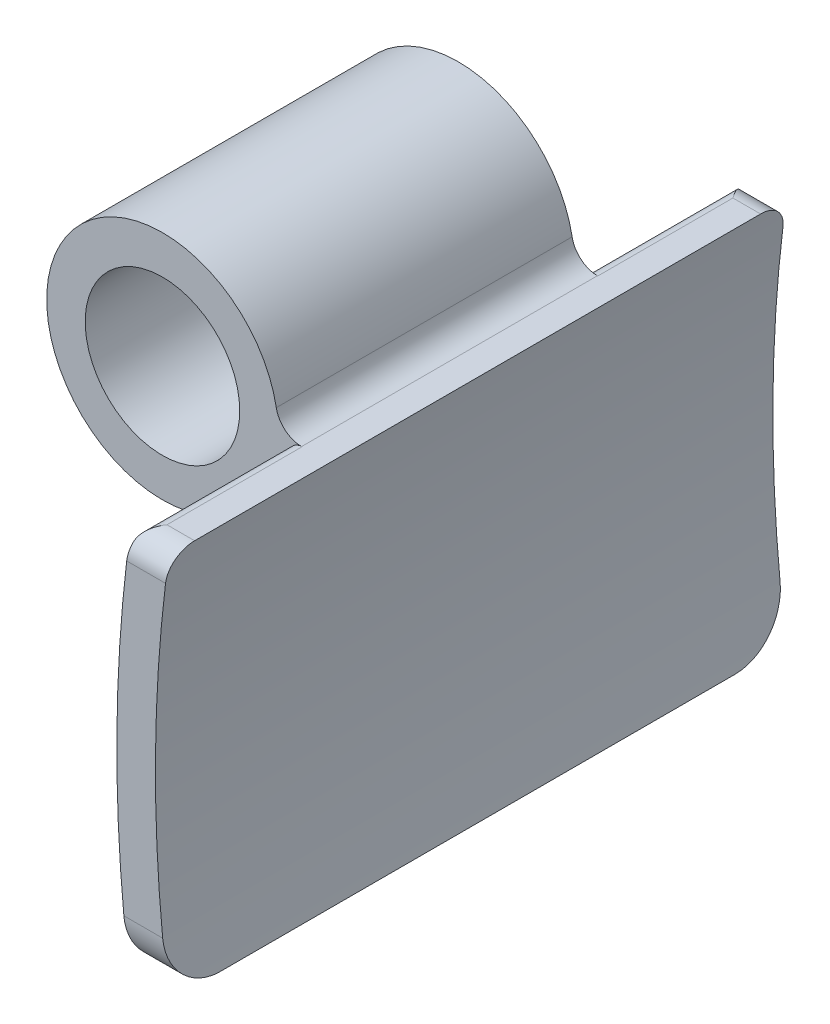
SolidWorks part; units mm, degrees
material "No.2 BRASS"
ref_plane "Front Plane" through (0, 0, 0) normal (0, 0, 1) x (1, 0, 0)
ref_plane "Top Plane" through (0, 0, 0) normal (0, 1, 0) x (1, 0, 0)
ref_plane "Right Plane" through (0, 0, 0) normal (1, 0, 0) x (0, 0, -1)
sketch "Sketch1" plane through (0, 0, 0) normal (0, 0, 1) x (1, 0, 0)
  line L0 (1.4037, 19.6911) -> (4.8697, 19.6911)
  line L1 (4.8697, -27.9339) -> (0.0619, -27.9339)
  arc A0 (4.8697, 19.6911) -> (4.8697, -27.9339) centre (174.658, -4.1214) ccw
  arc A1 (-1.7184, 22.2889) -> (-8.5674, 7.3507) centre (-15.7678, 19.6911) ccw
  arc A2 (-1.4087, 3.0435) -> (0.0619, -27.9339) centre (174.658, -4.1214) ccw
  arc A3 (-8.5674, 7.3507) -> (-1.4087, 3.0435) centre (-6.1673, 3.2372) cw
  arc A4 (1.4037, 19.6911) -> (-1.7184, 22.2889) centre (1.4037, 22.8661) cw
  arc A5 (0.1534, 20.3526) -> (0.1534, -28.5953) centre (174.658, -4.1214) ccw construction
  point P14 (-1.4803, 19.6911)
  dimension "D1" = 171.45
  dimension "D2" = 28.575
  dimension "D5" = 4.7625
  dimension "D6" = 3.175
  dimension "D3" = 20.6375
  dimension "D7" = 47.625
  dimension "D8" = 23.8125
  dimension "D4" = 4.7625
extrude "Boss-Extrude1" add sketch "Sketch1" along normal mid plane 36.5125
sketch "Sketch2" plane through (0, 0, 18.2562) normal (0, 0, 1) x (1, 0, 0)
  arc A0 (-1.7184, 22.2889) -> (-8.5674, 7.3507) centre (-15.7678, 19.6911) ccw construction
  arc A1 (-1.7184, 22.2889) -> (-8.5674, 7.3507) centre (-15.7678, 19.6911) ccw
  circle A2 centre (-15.7678, 19.6911) radius 9.5377
  dimension "D1" = 19.0754
extrude "Cut-Extrude1" cut sketch "Sketch2" against normal through all contours A2
sketch "Sketch4" plane through (0, 0, 18.2562) normal (0, 0, 1) x (1, 0, 0)
  line L0 (0.0619, -27.9339) -> (4.8697, -27.9339) construction
  line L1 (4.8697, 19.6911) -> (1.4037, 19.6911) construction
  line L2 (0.0619, -27.9339) -> (4.8697, -27.9339)
  line L3 (4.8697, 19.6911) -> (1.4037, 19.6911)
  line L4 (4.8697, 19.6911) -> (0.1534, 20.3526)
  line L5 (4.8697, -27.9339) -> (0.1534, -28.5953)
  arc A1 (-1.4087, 3.0435) -> (-8.5674, 7.3507) centre (-6.1673, 3.2372) ccw construction
  arc A2 (-1.4087, 3.0435) -> (0.0619, -27.9339) centre (174.658, -4.1214) ccw construction
  arc A3 (4.8697, 19.6911) -> (4.8697, -27.9339) centre (174.658, -4.1214) ccw construction
  arc A4 (-1.7184, 22.2889) -> (1.4037, 19.6911) centre (1.4037, 22.8661) ccw construction
  arc A5 (-1.7184, 22.2889) -> (-8.5674, 7.3507) centre (-15.7678, 19.6911) ccw construction
  arc A6 (-1.4087, 3.0435) -> (-8.5674, 7.3507) centre (-6.1673, 3.2372) ccw
  arc A7 (-1.4087, 3.0435) -> (0.0619, -27.9339) centre (174.658, -4.1214) ccw
  arc A8 (4.8697, 19.6911) -> (4.8697, -27.9339) centre (174.658, -4.1214) ccw
  arc A9 (-1.7184, 22.2889) -> (1.4037, 19.6911) centre (1.4037, 22.8661) ccw
  arc A10 (-1.7184, 22.2889) -> (-8.5674, 7.3507) centre (-15.7678, 19.6911) ccw
  arc A11 (0.1534, 20.3526) -> (0.1534, -28.5953) centre (174.658, -4.1214) ccw
  arc M2 (4.8697, -27.9339) -> (4.8697, 19.6911) centre (174.658, -4.1214) cw
  arc M7 (-1.4087, 3.0435) -> (0.0619, -27.9339) centre (174.658, -4.1214) ccw
  line M8 (0.0619, -27.9339) -> (4.8697, -27.9339)
  dimension "D1" = 4.7625
extrude "Boss-Extrude2" add sketch "Sketch4" along normal blind 19.8438 contours L4 A11 M7 M8 M2
sketch "Sketch5" plane through (0, 0, -18.2562) normal (0, 0, -1) x (-1, 0, 0)
  line L0 (-0.0619, -27.9339) -> (-4.8697, -27.9339) construction
  line L1 (-4.8697, 19.6911) -> (-1.4037, 19.6911) construction
  line L2 (-4.8697, -27.9339) -> (-0.0619, -27.9339)
  line L3 (-1.4037, 19.6911) -> (-4.8697, 19.6911)
  line L4 (-4.8697, -27.9339) -> (-0.0619, -27.9339)
  line L5 (-1.4037, 19.6911) -> (-4.8697, 19.6911)
  line L6 (-4.8697, 19.6911) -> (-0.1534, 20.3526) construction
  line L7 (-4.8697, -27.9339) -> (-0.1534, -28.5953) construction
  line L8 (-0.0619, -27.9339) -> (-4.8697, -27.9339)
  line L9 (-4.8697, 19.6911) -> (-1.4037, 19.6911)
  line L10 (-4.8697, 19.6911) -> (-0.1534, 20.3526)
  line L11 (-4.8697, -27.9339) -> (-0.1534, -28.5953)
  arc A0 (-0.0619, -27.9339) -> (1.4087, 3.0435) centre (-174.658, -4.1214) ccw construction
  arc A1 (8.5674, 7.3507) -> (1.4087, 3.0435) centre (6.1673, 3.2372) ccw construction
  arc A2 (8.5674, 7.3507) -> (1.7184, 22.2889) centre (15.7678, 19.6911) ccw construction
  arc A3 (-1.4037, 19.6911) -> (1.7184, 22.2889) centre (-1.4037, 22.8661) ccw construction
  arc A4 (-0.1534, -28.5953) -> (-0.1534, 20.3526) centre (-174.658, -4.1214) ccw construction
  arc A5 (-4.8697, -27.9339) -> (-4.8697, 19.6911) centre (-174.658, -4.1214) ccw
  arc A6 (-0.0619, -27.9339) -> (1.4087, 3.0435) centre (-174.658, -4.1214) ccw
  arc A7 (8.5674, 7.3507) -> (1.4087, 3.0435) centre (6.1673, 3.2372) ccw
  arc A8 (8.5674, 7.3507) -> (1.7184, 22.2889) centre (15.7678, 19.6911) ccw
  arc A9 (-1.4037, 19.6911) -> (1.7184, 22.2889) centre (-1.4037, 22.8661) ccw
  arc A10 (-4.8697, -27.9339) -> (-4.8697, 19.6911) centre (-174.658, -4.1214) ccw
  arc A11 (-0.0619, -27.9339) -> (1.4087, 3.0435) centre (-174.658, -4.1214) ccw
  arc A12 (8.5674, 7.3507) -> (1.4087, 3.0435) centre (6.1673, 3.2372) ccw
  arc A13 (8.5674, 7.3507) -> (1.7184, 22.2889) centre (15.7678, 19.6911) ccw
  arc A14 (-1.4037, 19.6911) -> (1.7184, 22.2889) centre (-1.4037, 22.8661) ccw
  arc A15 (-4.8697, -27.9339) -> (-4.8697, 19.6911) centre (-174.658, -4.1214) ccw construction
  arc A16 (-0.0619, -27.9339) -> (1.4087, 3.0435) centre (-174.658, -4.1214) ccw
  arc A17 (8.5674, 7.3507) -> (1.4087, 3.0435) centre (6.1673, 3.2372) ccw
  arc A18 (8.5674, 7.3507) -> (1.7184, 22.2889) centre (15.7678, 19.6911) ccw
  arc A19 (-1.4037, 19.6911) -> (1.7184, 22.2889) centre (-1.4037, 22.8661) ccw
  arc A20 (-0.1534, -28.5953) -> (-0.1534, 20.3526) centre (-174.658, -4.1214) ccw
  arc A21 (-4.8697, -27.9339) -> (-4.8697, 19.6911) centre (-174.658, -4.1214) ccw
  arc M9 (-4.8697, 19.6911) -> (-4.8697, -27.9339) centre (-174.658, -4.1214) cw
  line M10 (-4.8697, -27.9339) -> (-0.0619, -27.9339)
  arc M11 (-0.0619, -27.9339) -> (1.4087, 3.0435) centre (-174.658, -4.1214) ccw
  dimension "D1" = 0
extrude "Boss-Extrude3" add sketch "Sketch5" along normal blind 19.8438 contours A20 L10 M11 M9 M10
fillet "Fillet2" radius 6.35 2 edges at (2.4658, -27.9339, -38.1) (2.4658, -27.9339, 38.1)
fillet "Fillet3" radius 3.175 1 edges at (0.0619, -27.9339, 0)
fillet "Fillet5" radius 1.5875 2 edges at (0.1003, 19.971, 28.1781) (0.1003, 19.971, -28.1781)
fillet "Fillet6" radius 3.175 2 edges at (3.1614, 19.6911, 38.1) (3.1614, 19.6911, -38.1)
